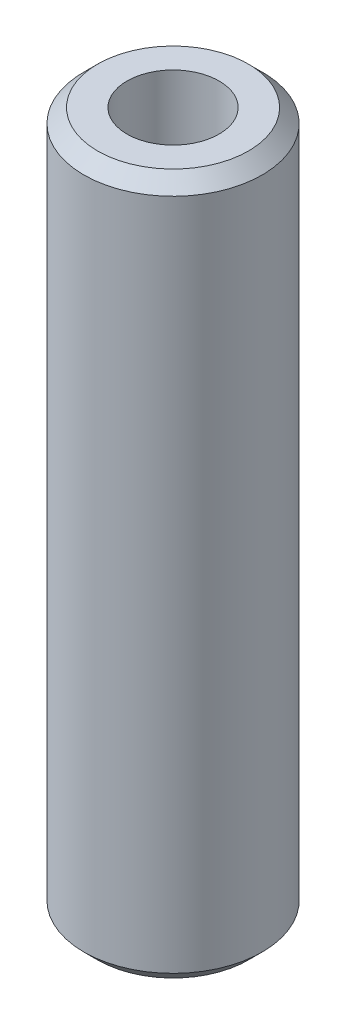
SolidWorks part; units mm, degrees
ref_plane "Front Plane" through (0, 0, 0) normal (0, 0, 1) x (1, 0, 0)
ref_plane "Top Plane" through (0, 0, 0) normal (0, 1, 0) x (1, 0, 0)
ref_plane "Right Plane" through (0, 0, 0) normal (1, 0, 0) x (0, 0, -1)
sketch "Sketch1" plane through (0, 0, 0) normal (0, 1, 0) x (1, 0, 0)
  circle A0 centre (0, 0) radius 12.5
  dimension "SHAFT_OD" = 25
extrude "Boss-Extrude1" add sketch "Sketch1" along normal blind 98.1938
sketch "Sketch2" plane through (0, 0, 0) normal (0, 1, 0) x (1, 0, 0)
  circle A0 centre (0, 0) radius 6.4536
  dimension "BORE_D" = 12.9073
extrude "Cut-Extrude1" cut sketch "Sketch2" along normal through all
chamfer "Chamfer1" distance 1.9354 angle 45 2 edges at (0, 98.1938, 12.5) (0, 0, 12.5)
